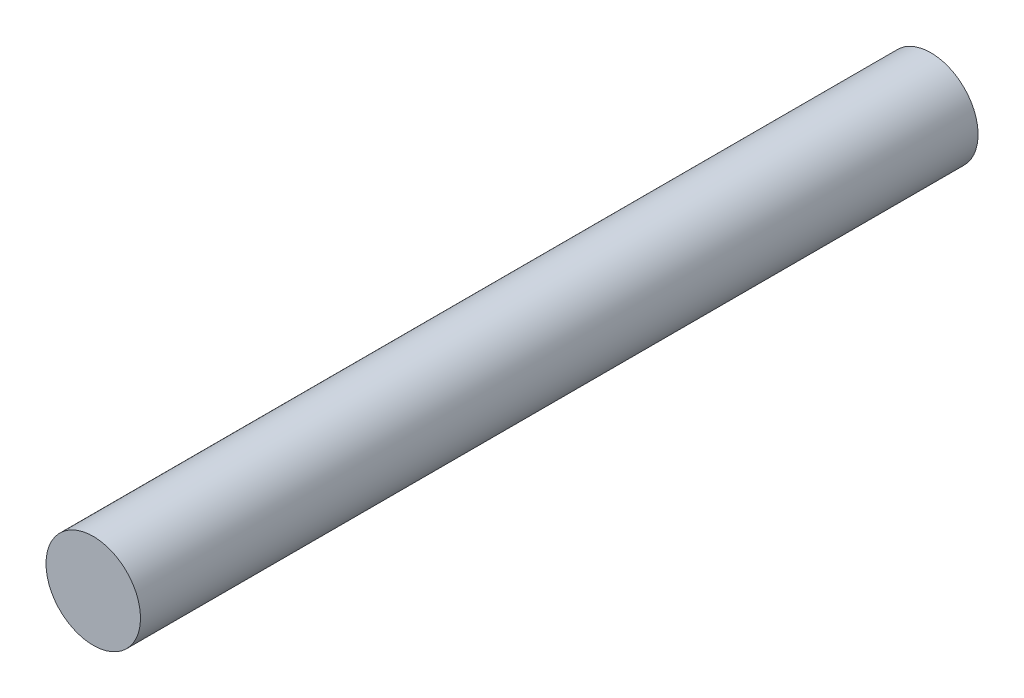
SolidWorks part; units mm, degrees
ref_plane "Front Plane" through (0, 0, 0) normal (0, 0, 1) x (1, 0, 0)
ref_plane "Top Plane" through (0, 0, 0) normal (0, 1, 0) x (1, 0, 0)
ref_plane "Right Plane" through (0, 0, 0) normal (1, 0, 0) x (0, 0, -1)
sketch "Sketch1" plane through (0, 0, 0) normal (0, 0, 1) x (1, 0, 0)
  circle A0 centre (0, 0) radius 1.94
  dimension "D1" = 3.88
extrude "Boss-Extrude1" add sketch "Sketch1" along normal blind 34.4
